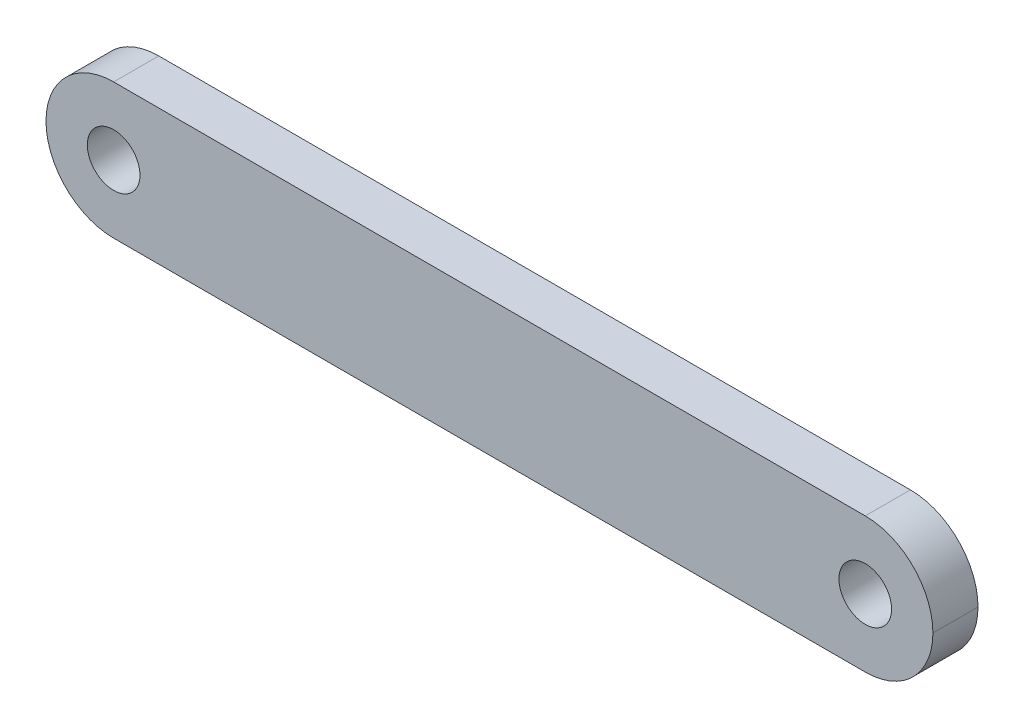
SolidWorks part; units mm, degrees
ref_plane "Front" through (0, 0, 0) normal (0, 0, 1) x (1, 0, 0)
ref_plane "Top" through (0, 0, 0) normal (0, 1, 0) x (1, 0, 0)
ref_plane "Right" through (0, 0, 0) normal (1, 0, 0) x (0, 0, -1)
sketch "Esquisse1" plane through (0, 0, 0) normal (0, 0, 1) x (1, 0, 0)
  line L0 (0, 9) -> (9, 9) construction
  line L1 (0, 0) -> (118, 0)
  line L2 (0, 0) -> (0, 18)
  line L3 (0, 18) -> (118, 18)
  line L4 (118, 0) -> (118, 18)
  line L5 (59, 0) -> (59, 18) construction
  circle A0 centre (9, 9) radius 3.5
  circle A1 centre (109, 9) radius 3.5
  dimension "D2" = 7
  dimension "D4" = 100
  dimension "D1" = 18
  dimension "D3" = 9
extrude "Boss.-Extru.1" add sketch "Esquisse1" along normal blind 6
fillet "Congé1" radius 9 4 edges at (118, 18, 3) (118, 0, 3) (0, 0, 3) (0, 18, 3)
